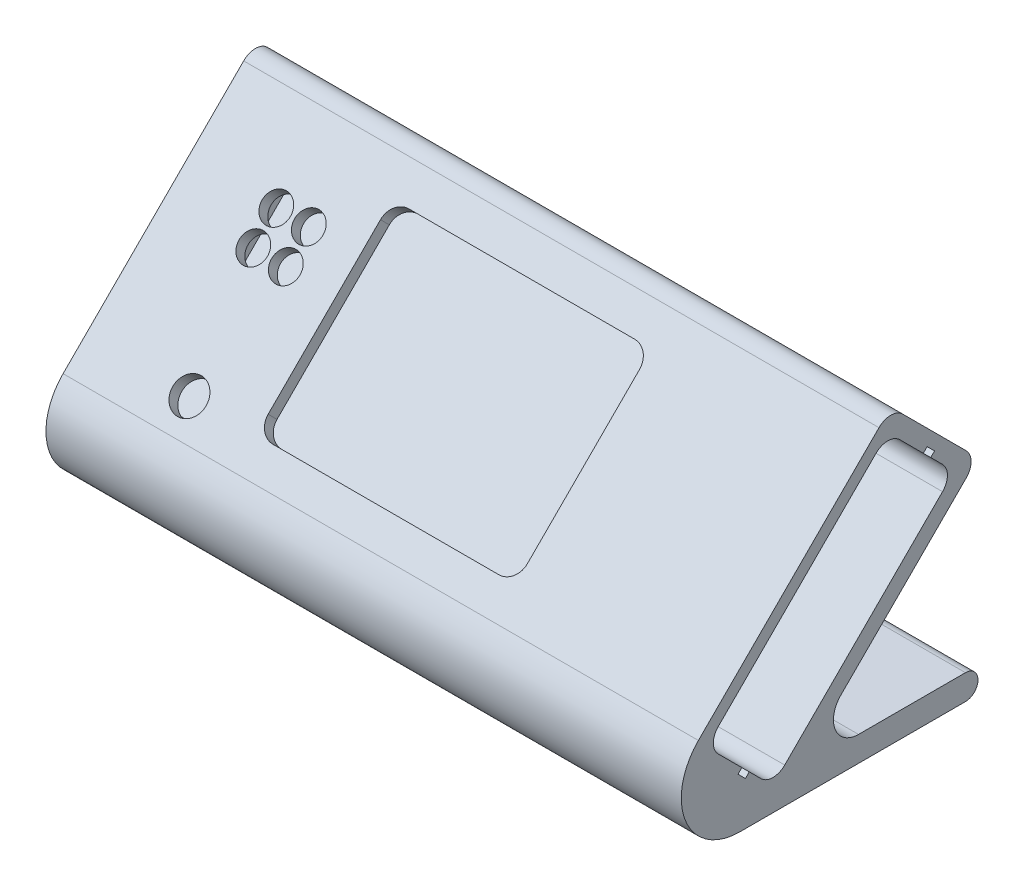
SolidWorks part; units mm, degrees
ref_plane "Front Plane" through (0, 0, 0) normal (0, 0, 1) x (1, 0, 0)
ref_plane "Top Plane" through (0, 0, 0) normal (0, 1, 0) x (1, 0, 0)
ref_plane "Right Plane" through (0, 0, 0) normal (1, 0, 0) x (0, 0, -1)
sketch "Sketch1" plane through (0, 0, 0) normal (1, 0, 0) x (0, 0, -1)
  line L0 (0, 0) -> (21.7082, 21.7082)
  line L1 (0, 0) -> (-2.8284, 2.8284)
  line L2 (-2.8284, 2.8284) -> (-3.288, 2.3688)
  line L3 (-3.288, 2.3688) -> (-4.1719, 3.2527)
  line L4 (-4.1719, 3.2527) -> (-3.7123, 3.7123)
  line L5 (-3.7123, 3.7123) -> (-7.955, 7.955)
  line L6 (-7.955, 7.955) -> (13.7532, 29.6631)
  line L7 (13.7532, 29.6631) -> (17.9959, 25.4205)
  line L8 (17.9959, 25.4205) -> (18.4555, 25.8801)
  line L9 (18.4555, 25.8801) -> (19.3394, 24.9962)
  line L10 (19.3394, 24.9962) -> (18.8798, 24.5366)
  line L11 (18.8798, 24.5366) -> (21.7082, 21.7082)
  line L12 (21.7082, 21.7082) -> (21.4815, 21.6406)
  line L13 (14.1068, 32.138) -> (-10.4298, 7.6014)
  line L15 (3, 0.1716) -> (24.5366, 21.7082)
  line L16 (14.1068, 32.138) -> (24.5366, 21.7082)
  line L17 (-10.4298, 7.6014) -> (-20.8597, -2.8284)
  line L18 (-20.8597, -2.8284) -> (0, -2.8284)
  line L19 (24.5366, -2.8284) -> (24.5366, 0.1716)
  line L20 (24.5366, 0.1716) -> (3, 0.1716)
  line L21 (0, -2.8284) -> (24.5366, -2.8284)
  dimension "D1" = 1.25
  dimension "D2" = 4
  dimension "D3" = 0.65
  dimension "D4" = 6
  dimension "D5" = 32
  dimension "D6" = 2
  dimension "D8" = 1.5
  dimension "D9" = 2
  dimension "D10" = 3
extrude "Boss-Extrude1" add sketch "Sketch1" along normal blind 74.5 contours L18 L21 L19 L20 L15 L16 L13 L17 L10 L11 L0 L1 L2 L3 L4 L5 L6 L7 L8 L9 region at (0, 26.5179, -18.9165)
fillet "Fillet1" radius 7 1 edges at (37.25, -2.8284, 20.8597)
fillet "Fillet2" radius 2 6 edges at (37.25, 0, 0) (37.25, 7.955, 7.955) (37.25, 21.7082, -21.7082) (37.25, 29.6631, -13.7532) (37.25, 21.7082, -24.5366) (37.25, 32.138, -14.1068)
fillet "Fillet3" radius 1.5 2 edges at (37.25, -2.8284, -24.5366) (37.25, 0.1716, -24.5366)
fillet "Fillet4" radius 3 1 edges at (37.25, 0.1716, -3)
sketch "Sketch3" plane through (0, 9.0156, 9.0156) normal (0, 0.7071, 0.7071) x (1, 0, 0)
  line L0 (0, 26.85) -> (74.5, 26.85) construction
  line L1 (0, 30.7) -> (0, 0.1495) construction
  line L2 (74.5, 30.7) -> (74.5, 0.1495) construction
  line L3 (74.5, 31.35) -> (0, 31.35) construction
  line L4 (0, 3.85) -> (74.5, 3.85) construction
  line L5 (11, 32.7) -> (11, -6.8505) construction
  line L6 (0, 32.7) -> (74.5, 32.7) construction
  line L7 (0, -6.8505) -> (74.5, -6.8505) construction
  line L8 (0, 3.85) -> (74.5, 3.85) construction
  line L9 (74.5, -0.65) -> (0, -0.65) construction
  line L10 (0, 19.35) -> (74.5, 19.35) construction
  line L11 (19, 32.7) -> (19, -6.8505) construction
  line L12 (50, 32.7) -> (50, -6.8505) construction
  line L13 (19, 26.85) -> (50, 26.85)
  line L14 (50, 26.85) -> (50, 3.85)
  line L15 (50, 3.85) -> (19, 3.85)
  line L16 (19, 3.85) -> (19, 26.85)
  line L17 (11, 19.35) -> (7.1109, 23.2391) construction
  line L18 (11, 23.2391) -> (14.8891, 19.35) construction
  line L19 (14.8891, 15.4609) -> (7.1109, 15.4609) construction
  line L20 (14.8891, 15.4609) -> (14.8891, 23.2391) construction
  line L21 (14.8891, 23.2391) -> (7.1109, 23.2391) construction
  line L22 (7.1109, 15.4609) -> (7.1109, 23.2391) construction
  line L23 (14.8891, 15.4609) -> (7.1109, 23.2391) construction
  line L24 (14.8891, 23.2391) -> (7.1109, 15.4609) construction
  line L25 (14.8891, 19.35) -> (11, 15.4609) construction
  line L26 (11, 15.4609) -> (7.1109, 19.35) construction
  line L27 (7.1109, 19.35) -> (11, 23.2391) construction
  circle A0 centre (11, 19.35) radius 5.5 construction
  circle A1 centre (11, 3.85) radius 2
  circle A2 centre (12.9445, 17.4055) radius 1.7
  circle A3 centre (12.9445, 21.2945) radius 1.7
  circle A4 centre (9.0555, 21.2945) radius 1.7
  circle A5 centre (9.0555, 17.4055) radius 1.7
  dimension "D8" = 11
  dimension "D9" = 4
  dimension "D10" = 3.4
  dimension "D1" = 4.5
  dimension "D2" = 23
  dimension "D3" = 11
  dimension "D4" = 4.5
  dimension "D5" = 12
  dimension "D6" = 19
  dimension "D7" = 31
extrude "Cut-Extrude1" cut sketch "Sketch3" against normal up to vertex (1.5 mm away) up to point (0, 28.2489, -12.339)
fillet "Fillet5" radius 2 4 edges at (50, 11.2076, 5.7629) (50, 27.4711, -10.5005) (19, 11.2076, 5.7629) (19, 27.4711, -10.5005)
sketch "Sketch4" plane through (0, 0, 0) normal (-1, 0, 0) x (0, 0, 1)
  line L5 (-23.0366, -2.8284) -> (3.9602, -2.8284)
  line L6 (8.9099, 9.1213) -> (-12.6926, 30.7238)
  line L7 (-15.521, 30.7238) -> (-23.1224, 23.1224)
  line L8 (-23.1224, 20.294) -> (-8.1213, 5.2929)
  line L9 (-10.2426, 0.1716) -> (-23.0366, 0.1716)
  line L10 (-23.0366, -2.8284) -> (3.9602, -2.8284)
  line L11 (8.9099, 9.1213) -> (-12.6926, 30.7238)
  line L12 (-15.521, 30.7238) -> (-23.1224, 23.1224)
  line L13 (-23.1224, 20.294) -> (-8.1213, 5.2929)
  line L14 (-10.2426, 0.1716) -> (-23.0366, 0.1716)
  arc A6 (-23.0366, 0.1716) -> (-24.5366, -1.3284) centre (-23.0366, -1.3284) ccw
  arc A7 (-24.5366, -1.3284) -> (-23.0366, -2.8284) centre (-23.0366, -1.3284) ccw
  arc A8 (3.9602, -2.8284) -> (8.9099, 9.1213) centre (3.9602, 4.1716) ccw
  arc A9 (-12.6926, 30.7238) -> (-15.521, 30.7238) centre (-14.1068, 29.3096) ccw
  arc A10 (-23.1224, 23.1224) -> (-23.1224, 20.294) centre (-21.7082, 21.7082) ccw
  arc A11 (-10.2426, 0.1716) -> (-8.1213, 5.2929) centre (-10.2426, 3.1716) ccw
  arc A12 (-23.0366, 0.1716) -> (-24.5366, -1.3284) centre (-23.0366, -1.3284) ccw
  arc A13 (-24.5366, -1.3284) -> (-23.0366, -2.8284) centre (-23.0366, -1.3284) ccw
  arc A14 (3.9602, -2.8284) -> (8.9099, 9.1213) centre (3.9602, 4.1716) ccw
  arc A15 (-12.6926, 30.7238) -> (-15.521, 30.7238) centre (-14.1068, 29.3096) ccw
  arc A16 (-23.1224, 23.1224) -> (-23.1224, 20.294) centre (-21.7082, 21.7082) ccw
  arc A17 (-10.2426, 0.1716) -> (-8.1213, 5.2929) centre (-10.2426, 3.1716) ccw
  dimension "D1" = 0
extrude "Boss-Extrude3" add sketch "Sketch4" along normal blind 1.5
